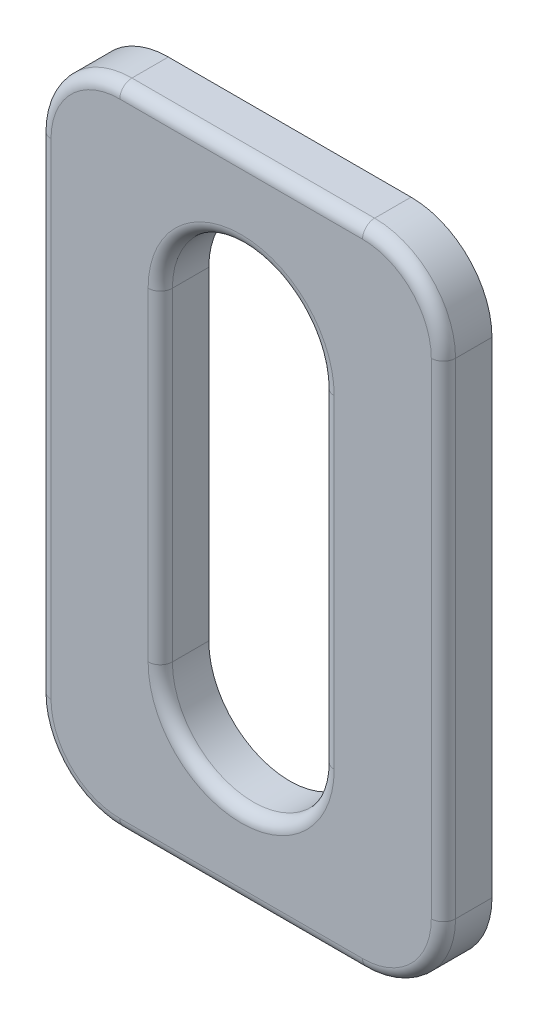
SolidWorks part; units mm, degrees
material "ABS"
ref_plane "Front Plane" through (0, 0, 0) normal (0, 0, 1) x (1, 0, 0)
ref_plane "Top Plane" through (0, 0, 0) normal (0, 1, 0) x (1, 0, 0)
ref_plane "Right Plane" through (0, 0, 0) normal (1, 0, 0) x (0, 0, -1)
sketch "Sketch1" plane through (0, 0, 0) normal (0, 0, 1) x (1, 0, 0)
  line L0 (12.5, 40) -> (12.5, 20) construction
  line L1 (0, 0) -> (25, 0)
  line L2 (0, 0) -> (0, 40)
  line L3 (0, 40) -> (25, 40)
  line L4 (25, 0) -> (25, 40)
  line L5 (12.5, 20) -> (12.5, 0) construction
  line L6 (12.5, 30) -> (12.5, 10) construction
  line L7 (17.5, 30) -> (17.5, 10)
  line L8 (7.5, 30) -> (7.5, 10)
  arc A0 (17.5, 30) -> (7.5, 30) centre (12.5, 30) ccw
  arc A1 (7.5, 10) -> (17.5, 10) centre (12.5, 10) ccw
  point P10 (12.5, 20)
  dimension "D3" = 5
  dimension "D1" = 25
  dimension "D2" = 40
extrude "Boss-Extrude1" add sketch "Sketch1" along normal blind 3
fillet "Fillet1" radius 5 4 edges at (25, 40, 1.5) (25, 0, 1.5) (0, 0, 1.5) (0, 40, 1.5)
fillet "Fillet2" radius 0.75 12 edges at (1.4645, 1.4645, 3) (0, 20, 3) (1.4645, 38.5355, 3) (23.5355, 38.5355, 3) (12.5, 40, 3) (25, 20, 3) (23.5355, 1.4645, 3) (12.5, 0, 3) (12.5, 5, 3) (17.5, 20, 3) (12.5, 35, 3) (7.5, 20, 3)
